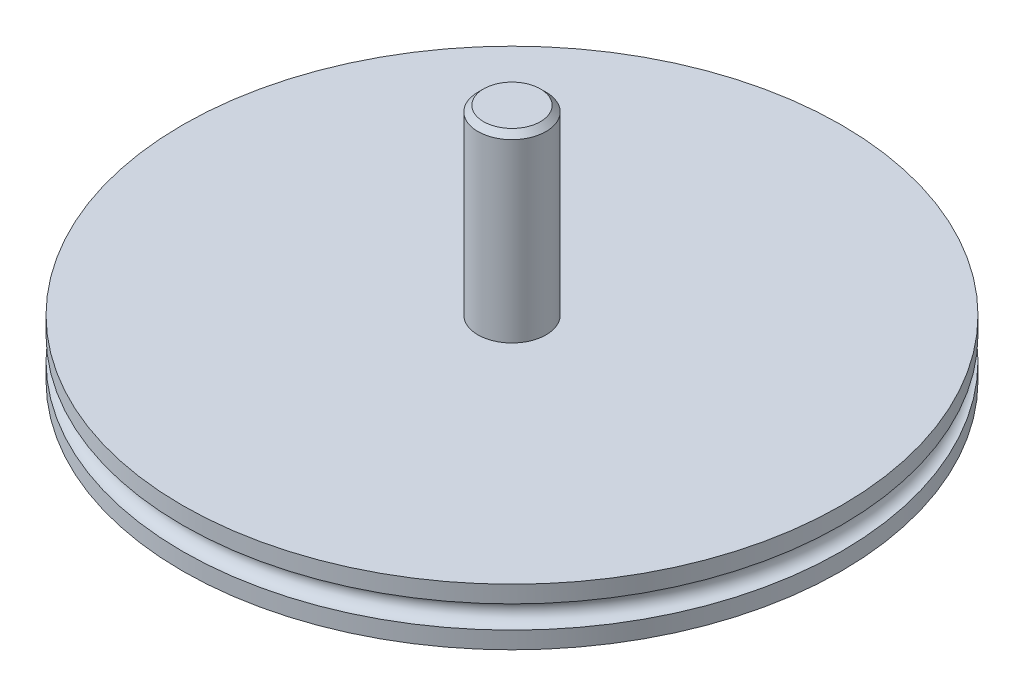
SolidWorks part; units mm, degrees
ref_plane "Plan de face" through (0, 0, 0) normal (0, 0, 1) x (1, 0, 0)
ref_plane "Plan de dessus" through (0, 0, 0) normal (0, 1, 0) x (1, 0, 0)
ref_plane "Plan de droite" through (0, 0, 0) normal (1, 0, 0) x (0, 0, -1)
sketch "Esquisse1" plane through (0, 0, 0) normal (0, 1, 0) x (1, 0, 0)
  circle A0 centre (0, 0) radius 3
  dimension "D1" = 6
extrude "Boss.-Extru.1" add sketch "Esquisse1" along normal blind 16
sketch "Esquisse4" plane through (0, 0, 0) normal (1, 0, 0) x (0, 0, -1)
  line L0 (0, 0) -> (29, 0)
  line L1 (29, 0) -> (29, -5) construction
  line L2 (29, -5) -> (0, -5)
  line L3 (0, -5) -> (0, 0)
  line L4 (29, -1.5) -> (29, 0)
  line L5 (29, -3.5) -> (29, -5)
  arc A0 (29, -1.5) -> (29, -3.5) centre (29, -2.5) ccw
  point P8 (29, -2.5)
  point P9 (30.0437, -5)
  point P10 (30, -3.5)
  dimension "D3" = 1
  dimension "D1" = 5
  dimension "D2" = 29
revolve "Révolution1" add sketch "Esquisse4" angle 360 about L3
chamfer "Chanfrein1" distance 0.5 angle 45 1 edges at (0, 16, 3)
